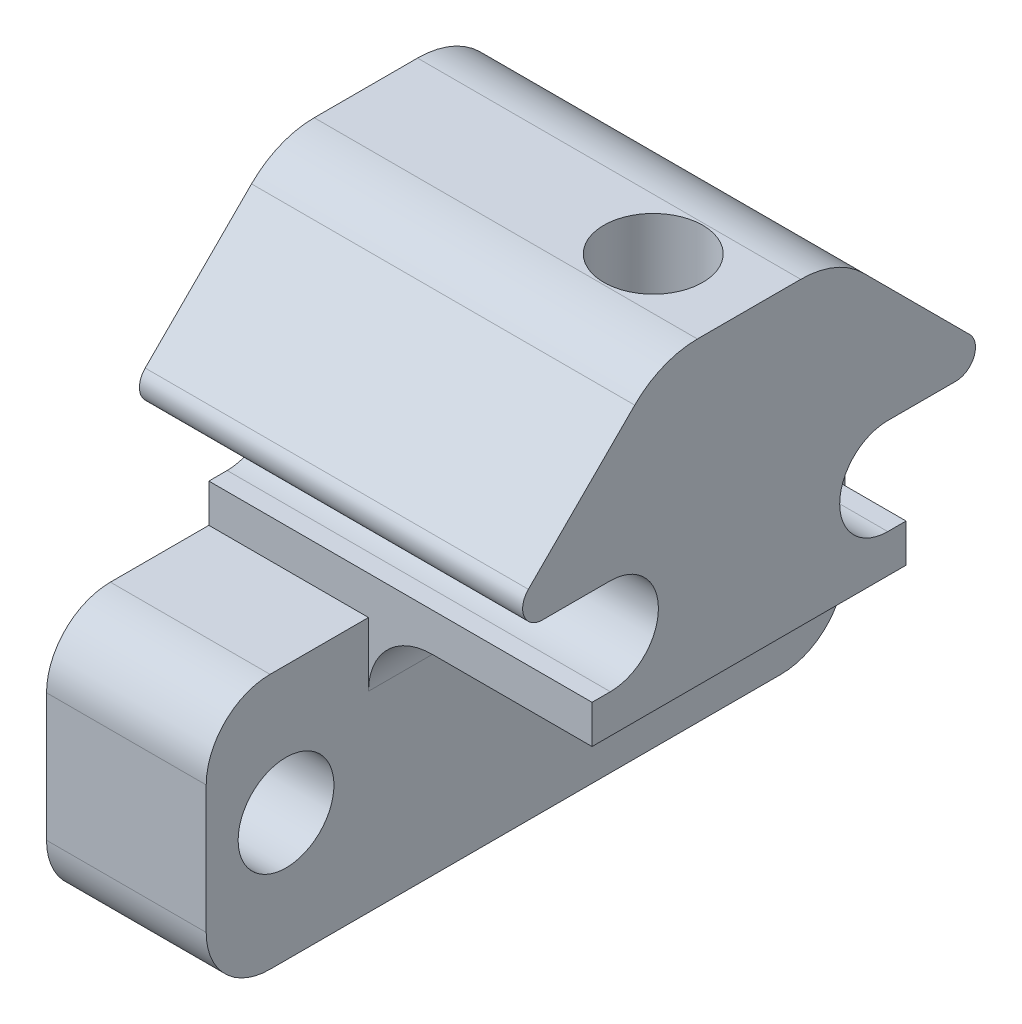
SolidWorks part; units mm, degrees
ref_plane "Front Plane" through (0, 0, 0) normal (0, 0, 1) x (1, 0, 0)
ref_plane "Top Plane" through (0, 0, 0) normal (0, 1, 0) x (1, 0, 0)
ref_plane "Right Plane" through (0, 0, 0) normal (1, 0, 0) x (0, 0, -1)
sketch "Sketch1" plane through (0, 0, 0) normal (1, 0, 0) x (0, 0, -1)
  line L0 (-5.3171, -3.1021) -> (-5.3171, -5.1021) construction
  line L1 (-5.3171, -5.1021) -> (5.3171, -5.1021) construction
  line L2 (5.3171, -5.1021) -> (5.3171, -3.1021) construction
  line L3 (-4.9171, -3.5021) -> (-4.3434, -3.5021)
  line L4 (-4.3434, -0.4923) -> (-6.4748, -0.4923)
  line L5 (-6.9104, 0.5593) -> (-3.5803, 3.8893)
  line L6 (-1.6181, 4.7021) -> (1.6181, 4.7021)
  line L7 (3.5803, 3.8893) -> (6.9104, 0.5593)
  line L8 (6.4748, -0.4923) -> (4.3434, -0.4923)
  line L9 (4.3434, -3.5021) -> (4.9171, -3.5021)
  line L10 (4.9171, -4.7021) -> (4.9171, -3.5021)
  line L11 (-4.9171, -4.7021) -> (4.9171, -4.7021)
  line L12 (-4.9171, -3.5021) -> (-4.9171, -4.7021)
  line L13 (-5.3171, -3.1021) -> (-4.3434, -3.1021) construction
  line L14 (-4.3434, -0.8923) -> (-6.4748, -0.8923) construction
  line L15 (-7.1932, 0.8421) -> (-3.8632, 4.1722) construction
  line L16 (-1.6181, 5.1021) -> (1.6181, 5.1021) construction
  line L17 (3.8632, 4.1722) -> (7.1932, 0.8421) construction
  line L18 (6.4748, -0.8923) -> (4.3434, -0.8923) construction
  line L19 (4.3434, -3.1021) -> (5.3171, -3.1021) construction
  arc A0 (-4.3434, -3.5021) -> (-4.3434, -0.4923) centre (-4.3434, -1.9972) ccw
  arc A1 (-6.9104, 0.5593) -> (-6.4748, -0.4923) centre (-6.4748, 0.1237) ccw
  arc A2 (-1.6181, 4.7021) -> (-3.5803, 3.8893) centre (-1.6181, 1.9271) ccw
  arc A3 (3.5803, 3.8893) -> (1.6181, 4.7021) centre (1.6181, 1.9271) ccw
  arc A4 (6.4748, -0.4923) -> (6.9104, 0.5593) centre (6.4748, 0.1237) ccw
  arc A5 (4.3434, -0.4923) -> (4.3434, -3.5021) centre (4.3434, -1.9972) ccw
  arc A6 (-4.3434, -3.1021) -> (-4.3434, -0.8923) centre (-4.3434, -1.9972) ccw construction
  arc A7 (-7.1932, 0.8421) -> (-6.4748, -0.8923) centre (-6.4748, 0.1237) ccw construction
  arc A8 (-1.6181, 5.1021) -> (-3.8632, 4.1722) centre (-1.6181, 1.9271) ccw construction
  arc A9 (3.8632, 4.1722) -> (1.6181, 5.1021) centre (1.6181, 1.9271) ccw construction
  arc A10 (6.4748, -0.8923) -> (7.1932, 0.8421) centre (6.4748, 0.1237) ccw construction
  arc A11 (4.3434, -0.8923) -> (4.3434, -3.1021) centre (4.3434, -1.9972) ccw construction
  dimension "D1" = 2
extrude "Boss-Extrude1" add sketch "Sketch1" along normal blind 12
sketch "Sketch2" plane through (0, -4.7021, 0) normal (0, -1, 0) x (1, 0, 0)
  line L1 (0, 10) -> (5, 10)
  line L2 (0, 10) -> (0, -10)
  line L3 (0, -10) -> (5, -10)
  line L4 (5, 10) -> (5, -10)
  line L5 (0, 0) -> (5, 0) construction
  point P4 (6.781, 10.7695)
  point P5 (5.0446, -4.3434)
  point P6 (0, 0)
  point P10 (0, 0)
  point P11 (6, 0)
  dimension "D1" = 5
  dimension "D2" = 20
extrude "Boss-Extrude2" add sketch "Sketch2" along normal blind 8
sketch "Sketch3" plane through (0, -4.7021, 0) normal (0, -1, 0) x (1, 0, 0)
  line L0 (0, 0) -> (9, 0) construction
  circle A0 centre (9, 0) radius 1.55
  dimension "D2" = 3.1
  dimension "D1" = 9
extrude "Cut-Extrude1" cut sketch "Sketch3" against normal through all
fillet "Fillet1" radius 2 5 edges at (5, -4.7021, 0) (2.5, -4.7021, 10) (2.5, -12.7021, 10) (2.5, -12.7021, -10) (2.5, -4.7021, -10)
sketch "Sketch5" plane through (0, 0, 0) normal (-1, 0, 0) x (0, 0, 1)
  line L0 (-7.5, -8.7021) -> (7.5, -8.7021) construction
  line L3 (0, 0) -> (0, -8.7021) construction
  line L4 (10, -10.7021) -> (10, -6.7021) construction
  circle A0 centre (-7.5, -8.7021) radius 1.5
  circle A1 centre (7.5, -8.7021) radius 1.5
  point P0 (0, -8.3318)
  point P1 (0, -8.7021)
  point P4 (10, -8.7021)
  dimension "D1" = 3
  dimension "D2" = 15
extrude "Cut-Extrude2" cut sketch "Sketch5" against normal through all
